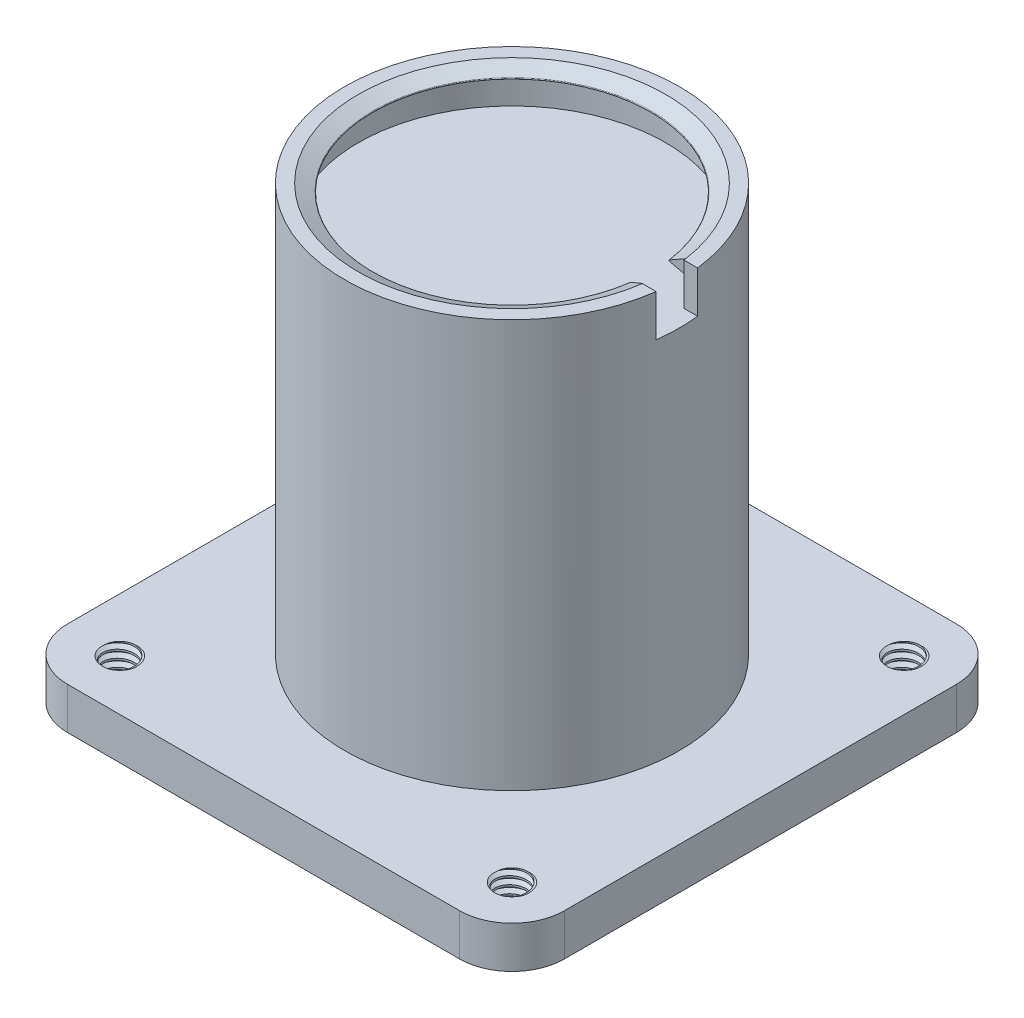
SolidWorks part; units mm, degrees
ref_plane "Front Plane" through (0, 0, 0) normal (0, 0, 1) x (1, 0, 0)
ref_plane "Top Plane" through (0, 0, 0) normal (0, 1, 0) x (1, 0, 0)
ref_plane "Right Plane" through (0, 0, 0) normal (1, 0, 0) x (0, 0, -1)
sketch "Sketch1" plane through (0, 0, 0) normal (0, 1, 0) x (1, 0, 0)
  line L1 (-37.5, -47.5) -> (37.5, -47.5)
  line L2 (-47.5, -37.5) -> (-47.5, 37.5)
  line L3 (-37.5, 47.5) -> (37.5, 47.5)
  line L4 (47.5, -37.5) -> (47.5, 37.5)
  line L5 (-47.5, -47.5) -> (47.5, 47.5) construction
  line L6 (-47.5, 47.5) -> (47.5, -47.5) construction
  circle A0 centre (0, 0) radius 29.4
  circle A1 centre (0, 0) radius 32
  arc A2 (37.5, -47.5) -> (47.5, -37.5) centre (37.5, -37.5) ccw
  arc A3 (-37.5, -47.5) -> (-47.5, -37.5) centre (-37.5, -37.5) cw
  arc A4 (37.5, 47.5) -> (47.5, 37.5) centre (37.5, 37.5) cw
  arc A5 (-47.5, 37.5) -> (-37.5, 47.5) centre (-37.5, 37.5) cw
  circle A6 centre (-37.5, 37.5) radius 3
  circle A7 centre (37.5, 37.5) radius 3
  circle A8 centre (-37.5, -37.5) radius 3
  circle A9 centre (37.5, -37.5) radius 3
  point P0 (0, 0)
  dimension "D3" = 58.8
  dimension "D4" = 64
  dimension "D5" = 10
  dimension "D6" = 6
  dimension "D1" = 95
  dimension "D2" = 95
extrude "Boss-Extrude2" add sketch "Sketch1" along normal blind 8 contours A5 L3 A4 L4 A2 L1 A3 L2
sketch "Sketch2" plane through (0, 8, 0) normal (0, 1, 0) x (1, 0, 0)
  line L4 (-47.5, 37.5) -> (-47.5, -37.5)
  line L5 (-37.5, -47.5) -> (37.5, -47.5)
  line L6 (47.5, -37.5) -> (47.5, 37.5)
  line L7 (37.5, 47.5) -> (-37.5, 47.5)
  line L8 (-47.5, 37.5) -> (-47.5, -37.5)
  line L9 (-37.5, -47.5) -> (37.5, -47.5)
  line L10 (47.5, -37.5) -> (47.5, 37.5)
  line L11 (37.5, 47.5) -> (-37.5, 47.5)
  circle A0 centre (0, 0) radius 29.4 construction
  circle A1 centre (0, 0) radius 32 construction
  circle A2 centre (0, 0) radius 29.4
  circle A3 centre (0, 0) radius 32
  arc A4 (-47.5, -37.5) -> (-37.5, -47.5) centre (-37.5, -37.5) ccw
  arc A5 (37.5, -47.5) -> (47.5, -37.5) centre (37.5, -37.5) ccw
  arc A6 (47.5, 37.5) -> (37.5, 47.5) centre (37.5, 37.5) ccw
  arc A7 (-37.5, 47.5) -> (-47.5, 37.5) centre (-37.5, 37.5) ccw
  arc A8 (-47.5, -37.5) -> (-37.5, -47.5) centre (-37.5, -37.5) ccw
  arc A9 (37.5, -47.5) -> (47.5, -37.5) centre (37.5, -37.5) ccw
  arc A10 (47.5, 37.5) -> (37.5, 47.5) centre (37.5, 37.5) ccw
  arc A11 (-37.5, 47.5) -> (-47.5, 37.5) centre (-37.5, 37.5) ccw
  dimension "D1" = 0
extrude "Boss-Extrude3" add sketch "Sketch2" along normal blind 70 contours A2
sketch "Sketch3" plane through (0, 8, 0) normal (0, 1, 0) x (1, 0, 0)
  line L4 (-47.5, 37.5) -> (-47.5, -37.5)
  line L5 (-37.5, -47.5) -> (37.5, -47.5)
  line L6 (47.5, -37.5) -> (47.5, 37.5)
  line L7 (37.5, 47.5) -> (-37.5, 47.5)
  line L8 (-47.5, 37.5) -> (-47.5, -37.5)
  line L9 (-37.5, -47.5) -> (37.5, -47.5)
  line L10 (47.5, -37.5) -> (47.5, 37.5)
  line L11 (37.5, 47.5) -> (-37.5, 47.5)
  circle A0 centre (0, 0) radius 32 construction
  circle A1 centre (0, 0) radius 29.4 construction
  circle A2 centre (0, 0) radius 32
  circle A3 centre (0, 0) radius 29.4
  arc A4 (-47.5, -37.5) -> (-37.5, -47.5) centre (-37.5, -37.5) ccw
  arc A5 (37.5, -47.5) -> (47.5, -37.5) centre (37.5, -37.5) ccw
  arc A6 (47.5, 37.5) -> (37.5, 47.5) centre (37.5, 37.5) ccw
  arc A7 (-37.5, 47.5) -> (-47.5, 37.5) centre (-37.5, 37.5) ccw
  arc A8 (-47.5, -37.5) -> (-37.5, -47.5) centre (-37.5, -37.5) ccw
  arc A9 (37.5, -47.5) -> (47.5, -37.5) centre (37.5, -37.5) ccw
  arc A10 (47.5, 37.5) -> (37.5, 47.5) centre (37.5, 37.5) ccw
  arc A11 (-37.5, 47.5) -> (-47.5, 37.5) centre (-37.5, 37.5) ccw
  circle M11 centre (0, 0) radius 29.4
  dimension "D1" = 0
extrude "Boss-Extrude4" add sketch "Sketch3" along normal blind 78 contours A2 M11
sketch "Sketch4" plane through (0, 86, 0) normal (0, 1, 0) x (1, 0, 0)
  line L2 (29.1655, 3.7058) -> (31.7847, 3.7058)
  line L3 (29.1023, -4.173) -> (31.7267, -4.173)
  circle A0 centre (0, 0) radius 29.4 construction
  circle A1 centre (0, 0) radius 32 construction
  arc A2 (31.9507, -1.7753) -> (31.9268, 2.1639) centre (0, 0) ccw
  arc A3 (29.3465, -1.7723) -> (29.3205, 2.1602) centre (0, 0) ccw
  circle A4 centre (0, 0) radius 32 construction
  circle A5 centre (0, 0) radius 29.4 construction
  arc A6 (31.7267, -4.173) -> (31.7847, 3.7058) centre (0, 0) ccw
  arc A7 (29.1023, -4.173) -> (29.1655, 3.7058) centre (0, 0) ccw
  point P0 (29.3205, 2.1602)
  point P1 (31.9268, 2.1639)
  point P2 (29.1655, 3.7058)
  point P4 (31.9507, -1.7753)
  point P7 (29.3465, -1.7723)
  point P12 (31.7847, 3.7058)
  point P13 (31.7267, -4.173)
  point P16 (29.1023, -4.173)
extrude "Cut-Extrude2" cut sketch "Sketch4" against normal blind 8 contours A6 L2 A7 L3
sketch "Sketch5" plane through (0, 8, 0) normal (0, 1, 0) x (1, 0, 0)
  line L4 (-47.5, 37.5) -> (-47.5, -37.5)
  line L5 (-37.5, -47.5) -> (37.5, -47.5)
  line L6 (47.5, -37.5) -> (47.5, 37.5)
  line L7 (37.5, 47.5) -> (-37.5, 47.5)
  line L8 (-47.5, 37.5) -> (-47.5, -37.5)
  line L9 (-37.5, -47.5) -> (37.5, -47.5)
  line L10 (47.5, -37.5) -> (47.5, 37.5)
  line L11 (37.5, 47.5) -> (-37.5, 47.5)
  circle A0 centre (-37.5, -37.5) radius 3 construction
  circle A1 centre (37.5, -37.5) radius 3 construction
  circle A2 centre (37.5, 37.5) radius 3 construction
  circle A3 centre (-37.5, 37.5) radius 3 construction
  arc A4 (-47.5, -37.5) -> (-37.5, -47.5) centre (-37.5, -37.5) ccw
  arc A5 (37.5, -47.5) -> (47.5, -37.5) centre (37.5, -37.5) ccw
  arc A6 (47.5, 37.5) -> (37.5, 47.5) centre (37.5, 37.5) ccw
  arc A7 (-37.5, 47.5) -> (-47.5, 37.5) centre (-37.5, 37.5) ccw
  arc A8 (-47.5, -37.5) -> (-37.5, -47.5) centre (-37.5, -37.5) ccw
  arc A9 (37.5, -47.5) -> (47.5, -37.5) centre (37.5, -37.5) ccw
  arc A10 (47.5, 37.5) -> (37.5, 47.5) centre (37.5, 37.5) ccw
  arc A11 (-37.5, 47.5) -> (-47.5, 37.5) centre (-37.5, 37.5) ccw
  circle A12 centre (-37.5, -37.5) radius 3
  circle A13 centre (37.5, -37.5) radius 3
  circle A14 centre (37.5, 37.5) radius 3
  circle A15 centre (-37.5, 37.5) radius 3
  dimension "D1" = 0
extrude "Cut-Extrude3" cut sketch "Sketch5" against normal blind 8 contours A12 | A15 | A13 | A14
thread "Thread1" pitch 1.5 start angle 0, offset 1.5, length 10, pitch 1.5, diameter 6
ref_plane "Plane1" through (-40.5, 9.5, -37.5) normal (0, 0, 1) x (-1, 0, 0)
sketch "Thread Profile1" plane through (-40.5, 9.5, -37.5) normal (0, 0, 1) x (-1, 0, 0)
  line L0 (0, 0) -> (0, 1.5) construction
  line L1 (0, 0) -> (0.8119, 0.4687)
  line L2 (0.8119, 0.4687) -> (0.8119, 0.6562)
  line L3 (0.8119, 0.6562) -> (0, 1.125)
  line L4 (0.8119, 0.5625) -> (0, 0.5625) construction
  line L11 (0, 0) -> (0, 1.125)
  point P2 (0, 0)
  dimension "Pitch" = 1.5
  dimension "Profile_Angle" = 60
  dimension "Profile_Land" = 0.1875
  dimension "Profile_Height" = 0.8119
thread "Thread3" pitch 1.5 profile "Thread Profile3" start angle 0, offset 1.5, length 10, pitch 1.5, diameter 6
ref_plane "Plane3" through (34.5, 9.5, -37.5) normal (0, 0, 1) x (-1, 0, 0)
sketch "Thread Profile3" plane through (34.5, 9.5, -37.5) normal (0, 0, 1) x (-1, 0, 0)
  line L0 (0, 0) -> (0, 1.5) construction
  line L1 (0, 0) -> (0.8119, 0.4687)
  line L2 (0.8119, 0.4687) -> (0.8119, 0.6562)
  line L3 (0.8119, 0.6562) -> (0, 1.125)
  line L4 (0.8119, 0.5625) -> (0, 0.5625) construction
  line L11 (0, 0) -> (0, 1.125)
  point P2 (0, 0)
  dimension "Pitch" = 1.5
  dimension "Profile_Angle" = 60
  dimension "Profile_Land" = 0.1875
  dimension "Profile_Height" = 0.8119
thread "Thread4" pitch 1.5 profile "Thread Profile4" start angle 0, offset 1.5, length 10, pitch 1.5, diameter 6
ref_plane "Plane4" through (34.5, 9.5, 37.5) normal (0, 0, 1) x (-1, 0, 0)
sketch "Thread Profile4" plane through (34.5, 9.5, 37.5) normal (0, 0, 1) x (-1, 0, 0)
  line L0 (0, 0) -> (0, 1.5) construction
  line L1 (0, 0) -> (0.8119, 0.4687)
  line L2 (0.8119, 0.4687) -> (0.8119, 0.6562)
  line L3 (0.8119, 0.6562) -> (0, 1.125)
  line L4 (0.8119, 0.5625) -> (0, 0.5625) construction
  line L11 (0, 0) -> (0, 1.125)
  point P2 (0, 0)
  dimension "Pitch" = 1.5
  dimension "Profile_Angle" = 60
  dimension "Profile_Land" = 0.1875
  dimension "Profile_Height" = 0.8119
thread "Thread5" pitch 1.5 profile "Thread Profile5" start angle 0, offset 1.5, length 10, pitch 1.5, diameter 6
ref_plane "Plane5" through (-40.5, 9.5, 37.5) normal (0, 0, 1) x (-1, 0, 0)
sketch "Thread Profile5" plane through (-40.5, 9.5, 37.5) normal (0, 0, 1) x (-1, 0, 0)
  line L0 (0, 0) -> (0, 1.5) construction
  line L1 (0, 0) -> (0.8119, 0.4687)
  line L2 (0.8119, 0.4687) -> (0.8119, 0.6562)
  line L3 (0.8119, 0.6562) -> (0, 1.125)
  line L4 (0.8119, 0.5625) -> (0, 0.5625) construction
  line L11 (0, 0) -> (0, 1.125)
  point P2 (0, 0)
  dimension "Pitch" = 1.5
  dimension "Profile_Angle" = 60
  dimension "Profile_Land" = 0.1875
  dimension "Profile_Height" = 0.8119
sketch "Sketch6" plane through (0, 0, 0) normal (0, 0, 1) x (1, 0, 0)
  line L0 (-29.4, 86) -> (-29.4, 78) construction
  line L1 (-29.4, 86) -> (-29.4, 83.3124)
  line L2 (-29.4, 86) -> (-26.6551, 84.6276)
  line L4 (-26.6551, 84.399) -> (-29.4, 83.3124)
  arc A1 (-26.6551, 84.399) -> (-26.6551, 84.6276) centre (-26.6961, 84.5133) ccw
  point P2 (-29.4, 84.5)
  point P5 (-26.4, 84.5)
  dimension "D1" = 8
  dimension "D2" = 6.5
  dimension "D3" = 3
sketch "Sketch7" plane through (0, 0, 0) normal (0, 0, 1) x (1, 0, 0)
  line L0 (0, 0) -> (0, 15.4194)
  line L1 (-37.5, 0) -> (37.5, 0) construction
revolve "Revolve1" add sketch "Sketch6" angle 172 about L0
